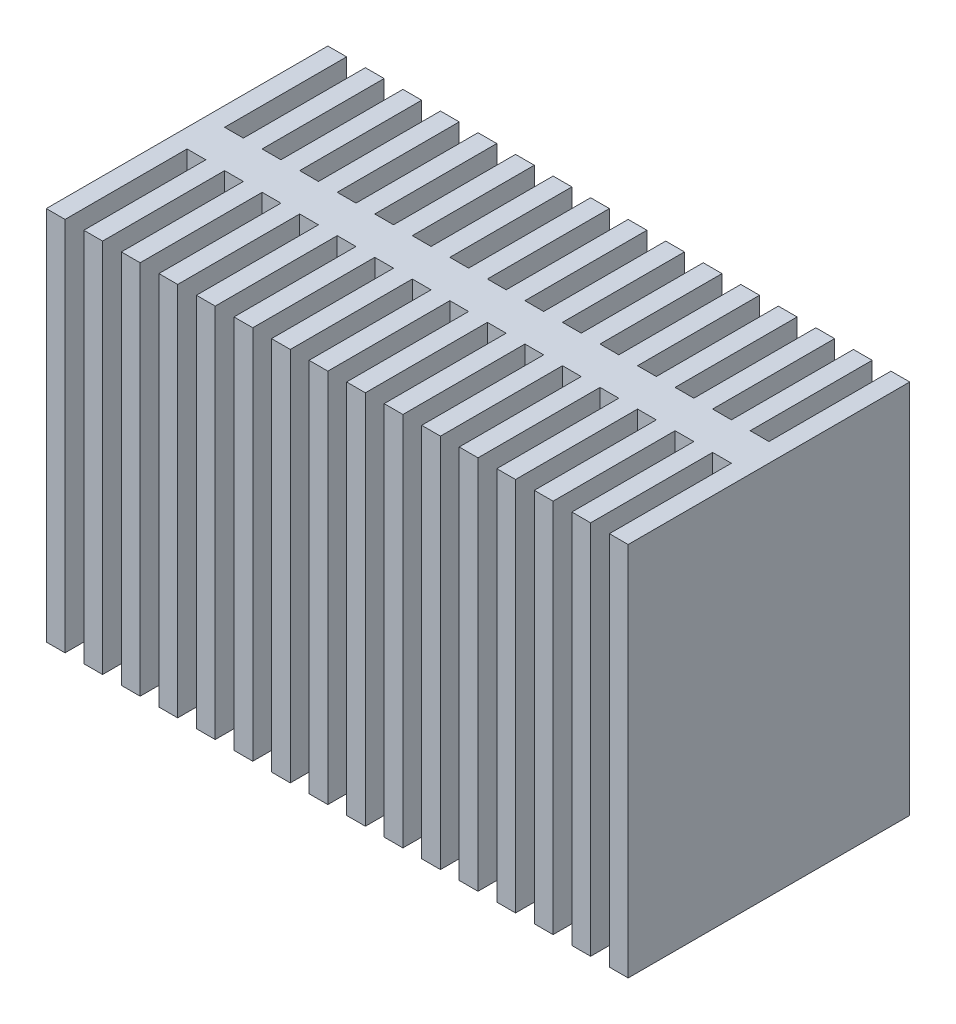
SolidWorks part; units mm, degrees
ref_plane "Front Plane" through (0, 0, 0) normal (0, 0, 1) x (1, 0, 0)
ref_plane "Top Plane" through (0, 0, 0) normal (0, 1, 0) x (1, 0, 0)
ref_plane "Right Plane" through (0, 0, 0) normal (1, 0, 0) x (0, 0, -1)
sketch "Sketch2" plane through (0, 0, 0) normal (0, 1, 0) x (1, 0, 0)
  line L0 (0, 0) -> (0, -15)
  line L1 (0, -15) -> (1, -15)
  line L2 (1, -15) -> (1, -8.5)
  line L3 (1, -8.5) -> (2, -8.5)
  line L4 (2, -8.5) -> (2, -6.5)
  line L5 (2, -6.5) -> (1, -6.5)
  line L6 (1, -6.5) -> (1, 0)
  line L7 (1, 0) -> (0, 0)
  line L8 (3, 0) -> (2, 0)
  line L9 (2, 0) -> (2, -15)
  line L10 (2, -15) -> (3, -15)
  line L11 (3, -15) -> (3, -8.5)
  line L12 (3, -8.5) -> (4, -8.5)
  line L13 (4, -8.5) -> (4, -6.5)
  line L14 (4, -6.5) -> (3, -6.5)
  line L15 (3, -6.5) -> (3, 0)
  line L16 (5, 0) -> (4, 0)
  line L17 (4, 0) -> (4, -15)
  line L18 (4, -15) -> (5, -15)
  line L19 (5, -15) -> (5, -8.5)
  line L20 (5, -8.5) -> (6, -8.5)
  line L21 (6, -8.5) -> (6, -6.5)
  line L22 (6, -6.5) -> (5, -6.5)
  line L23 (5, -6.5) -> (5, 0)
  line L24 (7, 0) -> (6, 0)
  line L25 (6, 0) -> (6, -15)
  line L26 (6, -15) -> (7, -15)
  line L27 (7, -15) -> (7, -8.5)
  line L28 (7, -8.5) -> (8, -8.5)
  line L29 (8, -8.5) -> (8, -6.5)
  line L30 (8, -6.5) -> (7, -6.5)
  line L31 (7, -6.5) -> (7, 0)
  line L32 (9, 0) -> (8, 0)
  line L33 (8, 0) -> (8, -15)
  line L34 (8, -15) -> (9, -15)
  line L35 (9, -15) -> (9, -8.5)
  line L36 (9, -8.5) -> (10, -8.5)
  line L37 (10, -8.5) -> (10, -6.5)
  line L38 (10, -6.5) -> (9, -6.5)
  line L39 (9, -6.5) -> (9, 0)
  line L40 (11, 0) -> (10, 0)
  line L41 (10, 0) -> (10, -15)
  line L42 (10, -15) -> (11, -15)
  line L43 (11, -15) -> (11, -8.5)
  line L44 (11, -8.5) -> (12, -8.5)
  line L45 (12, -8.5) -> (12, -6.5)
  line L46 (12, -6.5) -> (11, -6.5)
  line L47 (11, -6.5) -> (11, 0)
  line L48 (12, -15) -> (12, 0)
  line L49 (12, 0) -> (13, 0)
  line L50 (13, 0) -> (13, -15)
  line L51 (13, -15) -> (12, -15)
  line L52 (13, 0) -> (12, 0)
  line L53 (12, 0) -> (12, -15)
  line L54 (12, -15) -> (13, -15)
  line L55 (13, -15) -> (13, -8.5)
  line L56 (13, -8.5) -> (14, -8.5)
  line L57 (14, -8.5) -> (14, -6.5)
  line L58 (14, -6.5) -> (13, -6.5)
  line L59 (13, -6.5) -> (13, 0)
  line L60 (15, 0) -> (14, 0)
  line L61 (14, 0) -> (14, -15)
  line L62 (14, -15) -> (15, -15)
  line L63 (15, -15) -> (15, -8.5)
  line L64 (15, -8.5) -> (16, -8.5)
  line L65 (16, -8.5) -> (16, -6.5)
  line L66 (16, -6.5) -> (15, -6.5)
  line L67 (15, -6.5) -> (15, 0)
  line L68 (17, 0) -> (16, 0)
  line L69 (16, 0) -> (16, -15)
  line L70 (16, -15) -> (17, -15)
  line L71 (17, -15) -> (17, -8.5)
  line L72 (17, -8.5) -> (18, -8.5)
  line L73 (18, -8.5) -> (18, -6.5)
  line L74 (18, -6.5) -> (17, -6.5)
  line L75 (17, -6.5) -> (17, 0)
  line L76 (19, 0) -> (18, 0)
  line L77 (18, 0) -> (18, -15)
  line L78 (18, -15) -> (19, -15)
  line L79 (19, -15) -> (19, -8.5)
  line L80 (19, -8.5) -> (20, -8.5)
  line L81 (20, -8.5) -> (20, -6.5)
  line L82 (20, -6.5) -> (19, -6.5)
  line L83 (19, -6.5) -> (19, 0)
  line L84 (21, 0) -> (20, 0)
  line L85 (20, 0) -> (20, -15)
  line L86 (20, -15) -> (21, -15)
  line L87 (21, -15) -> (21, -8.5)
  line L88 (21, -8.5) -> (22, -8.5)
  line L89 (22, -8.5) -> (22, -6.5)
  line L90 (22, -6.5) -> (21, -6.5)
  line L91 (21, -6.5) -> (21, 0)
  line L92 (23, 0) -> (22, 0)
  line L93 (22, 0) -> (22, -15)
  line L94 (22, -15) -> (23, -15)
  line L95 (23, -15) -> (23, -8.5)
  line L96 (23, -8.5) -> (24, -8.5)
  line L97 (24, -8.5) -> (24, -6.5)
  line L98 (24, -6.5) -> (23, -6.5)
  line L99 (23, -6.5) -> (23, 0)
  line L100 (25, 0) -> (24, 0)
  line L101 (24, 0) -> (24, -15)
  line L102 (24, -15) -> (25, -15)
  line L103 (25, -15) -> (25, -8.5)
  line L104 (25, -8.5) -> (26, -8.5)
  line L105 (26, -8.5) -> (26, -6.5)
  line L106 (26, -6.5) -> (25, -6.5)
  line L107 (25, -6.5) -> (25, 0)
  line L108 (27, 0) -> (26, 0)
  line L109 (26, 0) -> (26, -15)
  line L110 (26, -15) -> (27, -15)
  line L111 (27, -15) -> (27, -8.5)
  line L112 (27, -8.5) -> (28, -8.5)
  line L113 (28, -8.5) -> (28, -6.5)
  line L114 (28, -6.5) -> (27, -6.5)
  line L115 (27, -6.5) -> (27, 0)
  line L116 (29, 0) -> (28, 0)
  line L117 (28, 0) -> (28, -15)
  line L118 (28, -15) -> (29, -15)
  line L119 (29, -15) -> (29, -8.5)
  line L120 (29, -8.5) -> (30, -8.5)
  line L121 (30, -8.5) -> (30, -6.5)
  line L122 (30, -6.5) -> (29, -6.5)
  line L123 (29, -6.5) -> (29, 0)
  line L124 (30, -8.5) -> (30, -15)
  line L125 (30, -15) -> (31, -15)
  line L126 (31, -15) -> (31, 0)
  line L127 (31, 0) -> (30, 0)
  line L128 (30, 0) -> (30, -6.5)
  line L129 (30, -6.5) -> (30, -8.5)
  line L130 (30, 0) -> (30, -15)
  dimension "D1" = 15
  dimension "D2" = 2
  dimension "D3" = 6.5
  dimension "D4" = 1
  dimension "D5" = 1
  dimension "D6" = 2
  dimension "D7" = 15
extrude "Boss-Extrude1" add sketch "Sketch2" along normal blind 20 contours L6 L7 L0 L1 L2 L3 L4 L5 | L14 L15 L8 L9 L4 L10 L11 L12 L13 | L22 L23 L16 L17 L13 L18 L19 L20 L21 | L30 L31 L24 L25 L21 L26 L27 L28 L29 | L38 L39 L32 L33 L29 L34 L35 L36 L37 | L46 L47 L40 L41 L37 L42 L43 L44 L45 | L51 L50 L49 L48 L45 | L127 L128 L121 L124 L125 L126 | L52 L53 L54 L55 L56 L57 L58 L59 | L60 L61 L62 L63 L64 L65 L66 L67 | L68 L69 L70 L71 L72 L73 L74 L75 | L76 L77 L78 L79 L80 L81 L82 L83 | L84 L85 L86 L87 L88 L89 L90 L91 | L92 L93 L94 L95 L96 L97 L98 L99 | L100 L101 L102 L103 L104 L105 L106 L107 | L108 L109 L110 L111 L112 L113 L114 L115 | L116 L117 L118 L119 L120 L121 L122 L123 region at (0.6176, 0, 7.5) region at (2.6176, 0, 7.5) region at (4.6176, 0, 7.5) region at (6.6176, 0, 7.5) region at (8.6176, 0, 7.5) region at (10.6176, 0, 7.5) region at (12.5, 0, 7.5) region at (30.5, 0, 7.5)
